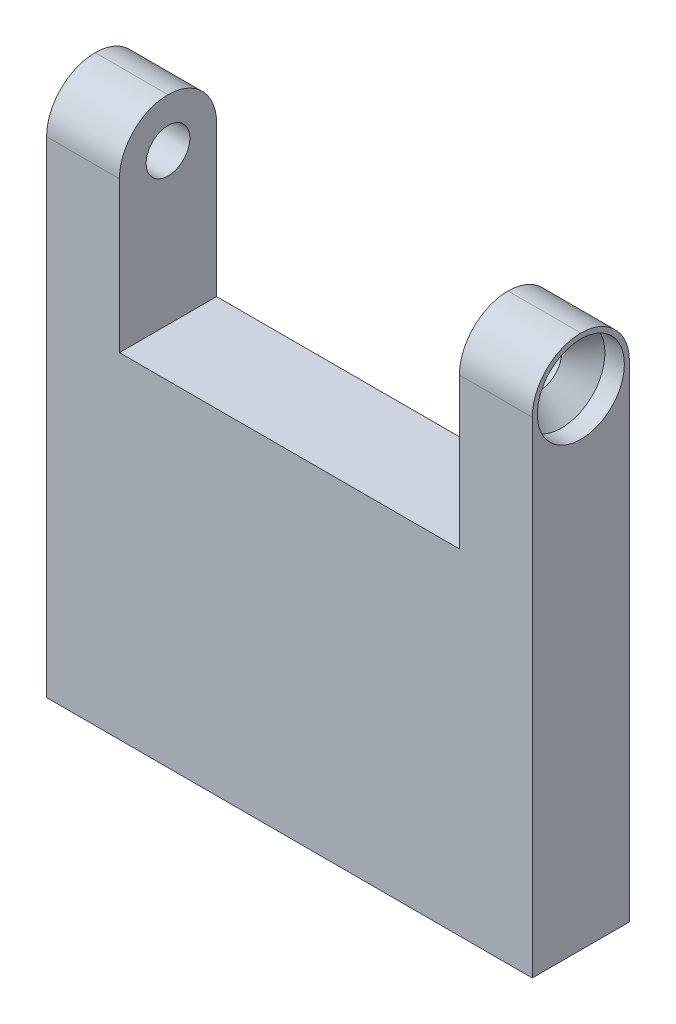
SolidWorks part; units mm, degrees
ref_plane "Front Plane" through (0, 0, 0) normal (0, 0, 1) x (1, 0, 0)
ref_plane "Top Plane" through (0, 0, 0) normal (0, 1, 0) x (1, 0, 0)
ref_plane "Right Plane" through (0, 0, 0) normal (1, 0, 0) x (0, 0, -1)
sketch "Sketch1" plane through (0, 0, 0) normal (0, 1, 0) x (1, 0, 0)
  line L1 (-25, -5) -> (25, -5)
  line L2 (-25, -5) -> (-25, 5)
  line L3 (-25, 5) -> (25, 5)
  line L4 (25, -5) -> (25, 5)
  line L5 (-25, -5) -> (25, 5) construction
  line L6 (-25, 5) -> (25, -5) construction
  point P0 (0, 0)
  dimension "D1" = 50
  dimension "D2" = 10
extrude "Boss-Extrude1" add sketch "Sketch1" along normal blind 55
fillet "Fillet1" radius 5 2 edges at (0, 55, -5) (0, 55, 5)
sketch "Sketch2" plane through (0, 0, 5) normal (0, 0, 1) x (1, 0, 0)
  line L0 (-25, 55) -> (25, 55) construction
  line L1 (-17.5, 55) -> (17.5, 55)
  line L2 (-17.5, 55) -> (-17.5, 34.5)
  line L3 (-17.5, 34.5) -> (17.5, 34.5)
  line L4 (17.5, 55) -> (17.5, 34.5)
  line L5 (-17.5, 55) -> (17.5, 34.5) construction
  line L6 (-17.5, 34.5) -> (17.5, 55) construction
  point P0 (0, 44.75)
  point P5 (0, 0)
  point P8 (0, 0)
  dimension "D1" = 35
  dimension "D2" = 20.5
extrude "Cut-Extrude1" cut sketch "Sketch2" against normal through all
hole_wizard "CSK for M4 SFHCS1" positions "Sketch3" profile "Sketch5" countersink size "M4" standard "ANSI Metric" end condition through all
sketch "Sketch3" plane through (-25, 0, 0) normal (-1, 0, 0) x (0, 0, 1)
  point P0 (0, 50)
sketch "Sketch5" plane through (-25, 50, 0) normal (0, 1, 0) x (0, 0, 1)
  line L0 (0, 0) -> (0, 50)
  line L1 (0, 50) -> (2.25, 50)
  line L2 (2.25, 50) -> (2.25, 4.23)
  line L3 (2.25, 4.23) -> (4.48, 2)
  line L4 (4.48, 2) -> (4.48, 0)
  line L6 (4.48, 0) -> (0, 0)
  line L7 (-2.25, 4.23) -> (-4.48, 2) construction
  line L11 (0, -6.35) -> (0, 107.95) construction
  dimension "Thru Hole Dia." = 4.5
  dimension "Thru Hole Depth" = 50
  dimension "C'Sink Dia." = 8.96
  dimension "C'Sink Angle" = 90
  dimension "Head Clearance" = 2
mirror "Mirror1" about plane through (0, 0, 0) normal (1, 0, 0) of "CSK for M4 SFHCS1"
hole_wizard "M4 Clearance Hole1" positions "Sketch6" profile "Sketch8" hole size "M4" standard "ANSI Metric"
sketch "Sketch6" plane through (0, 0, 0) normal (0, -1, 0) x (-1, 0, 0)
  line L0 (-20, 0) -> (20, 0)
  point P0 (-20, 0)
  point P1 (20, 0)
  point P3 (0, 0)
  dimension "D1" = 40
sketch "Sketch8" plane through (20, 0, 0) normal (1, 0, 0) x (0, 0, -1)
  line L0 (0, 0) -> (0, 10.3519)
  line L1 (0, 10.3519) -> (2.25, 9)
  line L2 (2.25, 9) -> (2.25, 0)
  line L5 (2.25, 0) -> (0, 0)
  line L10 (0, 10.3519) -> (-2.25, 9) construction
  line L11 (0, -6.35) -> (0, 107.95) construction
  dimension "Hole Dia." = 4.5
  dimension "Hole Depth" = 9
  dimension "Drill Angle" = 118
sketch "Sketch9" plane through (0, 0, -5) normal (0, 0, -1) x (-1, 0, 0)
  line L0 (17.75, 0) -> (22.25, 0) construction
  line L1 (16.3, 5) -> (23.7, 5)
  line L2 (16.3, 5) -> (16.3, 9)
  line L3 (16.3, 9) -> (23.7, 9)
  line L4 (23.7, 5) -> (23.7, 9)
  line L5 (16.3, 5) -> (23.7, 9) construction
  line L6 (16.3, 9) -> (23.7, 5) construction
  line L7 (17.75, 0) -> (22.25, 0)
  point P0 (20, 7)
  point P7 (0, 0)
  point P8 (20, 0)
  dimension "D1" = 4
  dimension "D2" = 7.4
  dimension "D3" = 9
extrude "Cut-Extrude2" cut sketch "Sketch9" against normal blind 9 contours L1 L4 L3 L2 region at (-20, 7, -5)
mirror "Mirror2" about plane through (0, 0, 0) normal (1, 0, 0) of "Cut-Extrude2"
